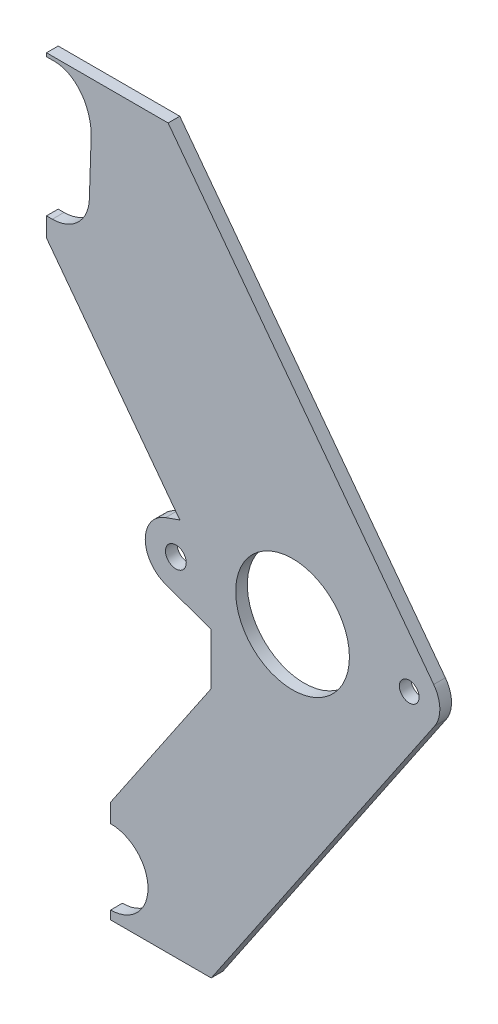
SolidWorks part; units mm, degrees
ref_plane "Front Plane" through (0, 0, 0) normal (0, 0, 1) x (1, 0, 0)
ref_plane "Top Plane" through (0, 0, 0) normal (0, 1, 0) x (1, 0, 0)
ref_plane "Right Plane" through (0, 0, 0) normal (1, 0, 0) x (0, 0, -1)
sketch "Sketch1" plane through (0, 0, 0) normal (0, 0, 1) x (1, 0, 0)
  line L4 (-42.5313, -7.0599) -> (-7.0875, -19.7678)
  line L6 (7.0875, -19.7678) -> (42.5312, -7.0599)
  line L10 (42.5313, 7.0599) -> (7.0875, 19.7678)
  line L12 (-43.5438, -9.8839) -> (-8.1, -22.5918)
  line L13 (8.1, -22.5918) -> (43.5437, -9.8839)
  line L14 (43.5437, 9.8839) -> (8.1, 22.5918)
  line L15 (-8.1, 22.5918) -> (-43.5438, 9.8839)
  line L16 (0, 0) -> (0, -103.21) construction
  line L17 (0, -103.21) -> (-62.35, -103.21) construction
  line L18 (-62.35, -83.9706) -> (-62.35, -90.41)
  line L19 (-62.35, -116.01) -> (-62.35, -118.9706)
  line L20 (-62.35, -118.9706) -> (-27.8815, -118.9706)
  line L21 (-27.8815, -118.9706) -> (48.6942, -5.8874)
  line L22 (-62.35, -83.9706) -> (-27.8815, -33.0692)
  line L23 (-27.8815, -33.0692) -> (-27.8815, -15.4994)
  line L24 (-40, 0) -> (40, 0) construction
  line L25 (0, 0) -> (0, 100) construction
  line L26 (0, 100) -> (-84.35, 100) construction
  line L27 (-84.35, 127.5) -> (-84.35, 72.5)
  line L28 (-84.35, 72.5) -> (-37.5566, 10.2117)
  line L29 (-84.35, 127.5) -> (-42.6503, 127.5)
  line L30 (-42.6503, 127.5) -> (48.395, 6.3067)
  line L32 (-7.0875, 19.7678) -> (-42.5312, 7.0599) construction
  circle A15 centre (-40, 0) radius 3.5658
  circle A16 centre (40, 0) radius 3.3865
  circle A17 centre (0, 0) radius 19.5
  arc A18 (-42.5312, 7.0599) -> (-42.5313, -7.0599) centre (-40, 0) ccw
  arc A19 (-7.0875, -19.7678) -> (7.0875, -19.7678) centre (0, 0) ccw
  arc A20 (42.5312, -7.0599) -> (42.5313, 7.0599) centre (40, 0) ccw
  arc A21 (7.0875, 19.7678) -> (-7.0875, 19.7678) centre (0, 0) ccw
  arc A22 (-8.1, -22.5918) -> (8.1, -22.5918) centre (0, 0) ccw
  arc A23 (43.5437, -9.8839) -> (43.5437, 9.8839) centre (40, 0) ccw
  arc A24 (8.1, 22.5918) -> (-8.1, 22.5918) centre (0, 0) ccw
  arc A25 (-43.5438, 9.8839) -> (-43.5438, -9.8839) centre (-40, 0) ccw
  circle A26 centre (-62.35, -103.21) radius 12.8
  point P36 (-62.35, -103.21)
  point P49 (-84.35, 100)
  dimension "D1" = 39
  dimension "D3" = 3
  dimension "D4" = 103.21
  dimension "D5" = 62.35
  dimension "D6" = 25.6
  dimension "D9" = 22
  dimension "D10" = 55
  dimension "D12" = 40
  dimension "D2" = 80
  dimension "D7" = 35
  dimension "D8" = 100
  dimension "D11" = 40
extrude "Boss-Extrude1" add sketch "Sketch1" along normal blind 4 contours A25 L15 A24 L14 A23 L30 L29 L27 L28 | L15 A25 L12 A22 L13 A23 L14 A24 A15 A16 A17 | A26 L19 L20 L21 A23 L13 A22 L12 L23 L22 L18 region at (-49.3817, 0, 0) region at (-16.9741, -63.3689, 0) region at (-35.0338, 67.3914, 0)
sketch "Sketch2" plane through (0, 0, 0) normal (0, 0, -1) x (-1, 0, 0)
  line L0 (82.35, 79.0815) -> (84.35, 79.0815)
  line L1 (84.35, 127.5) -> (84.35, 72.5) construction
  line L2 (69.6567, 91.368) -> (69.0474, 110.0678)
  line L3 (81.5573, 126.3039) -> (84.35, 126.3039)
  line L4 (84.35, 126.3039) -> (84.35, 79.0815)
  arc A0 (82.35, 104.4815) -> (82.35, 79.0815) centre (82.35, 91.7815) ccw
  arc A1 (69.6567, 91.368) -> (82.35, 79.0815) centre (82.35, 91.7815) ccw
  spline S0 degree 3 poles (72.4972, 99.7948) (63.6631, 111.6233) (68.6805, 126.3039) (81.5573, 126.3039) knots 0 0 0 0 1 1 1 1 weights 1 0.601909 0.601909 1
  spline S1 degree 3 poles (69.0474, 110.0678) (68.7199, 120.1212) (74.4511, 126.3039) (81.5573, 126.3039) knots 0.328308 0.328308 0.328308 0.328308 1 1 1 1 weights 0.736637 0.644818 0.732605 1
extrude "Cut-Extrude1" cut sketch "Sketch2" against normal up to surface (4 mm away) up to face at (-37.682, -15.8192, 4)
